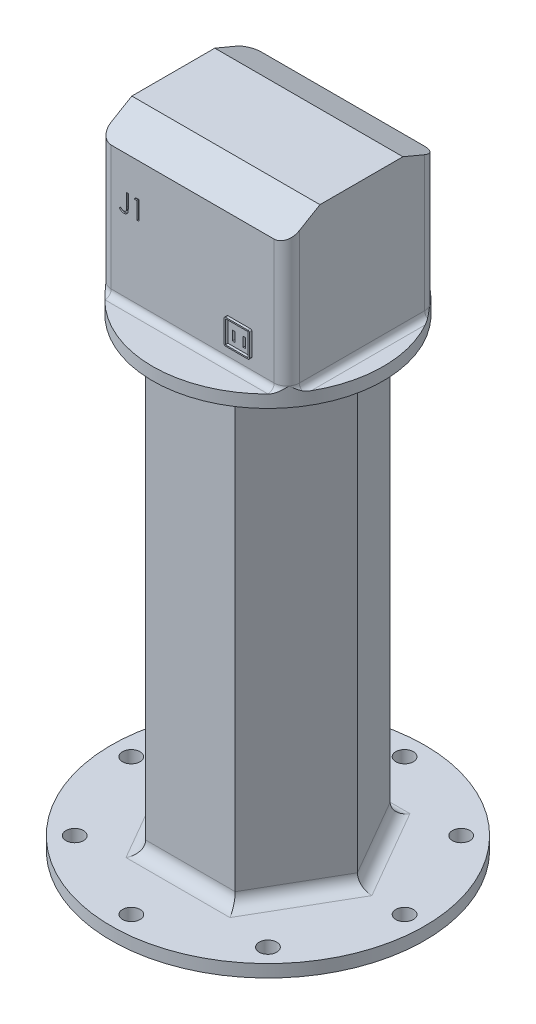
SolidWorks part; units mm, degrees
ref_plane "Alzado" through (0, 0, 0) normal (0, 0, 1) x (1, 0, 0)
ref_plane "Planta" through (0, 0, 0) normal (0, 1, 0) x (1, 0, 0)
ref_plane "Vista lateral" through (0, 0, 0) normal (1, 0, 0) x (0, 0, -1)
sketch "Sketch1" plane through (0, 0, 0) normal (0, 0, 1) x (1, 0, 0)
  line L1 (-75, -60) -> (75, -60)
  line L2 (-75, -60) -> (-75, 60)
  line L3 (-75, 60) -> (75, 60)
  line L4 (75, -60) -> (75, 60)
  line L5 (-75, -60) -> (75, 60) construction
  line L6 (-75, 60) -> (75, -60) construction
  point P0 (0, 0)
  dimension "D1" = 150
  dimension "D2" = 120
extrude "Boss-Extrude1" add sketch "Sketch1" along normal blind 60 and the other way blind 60
sketch "Sketch2" plane through (0, 0, 0) normal (0, 0, 1) x (1, 0, 0)
  line L5 (-75, 0) -> (-80, 0)
  line L6 (-75, 60) -> (-75, -60) construction
  line L7 (-80, 0) -> (-80, -36.1073)
  line L8 (-80, -36.1073) -> (-75, -44.4223)
  line L9 (-75, -44.4223) -> (-75, 0)
revolve "Revolve1" add sketch "Sketch2" angle 360 about L5
sketch "Sketch3" plane through (-80, 0, 0) normal (-1, 0, 0) x (0, 0, 1)
  circle A1 centre (0, 0) radius 12.5
  dimension "D1" = 25
extrude "Cut-Extrude2" cut sketch "Sketch3" against normal blind 10
sketch "Sketch4" plane through (0, -60, 0) normal (0, -1, 0) x (1, 0, 0)
  line L4 (69.9446, 45.0893) -> (69.9446, -45.0893)
  line L7 (-75, -60) -> (75, -60)
  line L12 (-75, -60) -> (-75, 60)
  line L13 (-75, 60) -> (75, 60)
  line L14 (75, -60) -> (75, 60)
  line L15 (1.8562, -5.2808) -> (58.2948, -49.733)
  line L16 (-58.2948, -49.733) -> (-1.8562, -5.2808)
  line L17 (-65.0883, -47.4461) -> (-7.8408, -2.3568)
  line L18 (-65.0883, 47.4461) -> (-7.8408, 2.3568)
  line L19 (-56.4386, -55.0898) -> (56.4386, -55.0898)
  line L20 (-69.9446, -45.0893) -> (-69.9446, 45.0893)
  line L21 (-56.4386, 55.0898) -> (56.4386, 55.0898)
  line L23 (-58.2948, 49.733) -> (-1.8562, 5.2808)
  line L26 (1.8562, 5.2808) -> (58.2948, 49.733)
  line L27 (7.8408, 2.3568) -> (65.0883, 47.4461)
  line L28 (7.8408, -2.3568) -> (65.0883, -47.4461)
  arc A4 (56.4386, -55.0898) -> (58.2948, -49.733) centre (56.4386, -52.0898) ccw
  arc A5 (69.9446, -45.0893) -> (65.0883, -47.4461) centre (66.9446, -45.0893) cw
  arc A6 (-56.4386, -55.0898) -> (-58.2948, -49.733) centre (-56.4386, -52.0898) cw
  arc A7 (-65.0883, -47.4461) -> (-69.9446, -45.0893) centre (-66.9446, -45.0893) cw
  arc A12 (7.8408, 2.3568) -> (7.8408, -2.3568) centre (9.697, 0) ccw
  arc A13 (1.8562, -5.2808) -> (-1.8562, -5.2808) centre (0, -7.6376) ccw
  arc A14 (-7.8408, -2.3568) -> (-7.8408, 2.3568) centre (-9.697, 0) ccw
  arc A15 (1.8562, 5.2808) -> (-1.8562, 5.2808) centre (0, 7.6376) cw
  arc A16 (69.9446, 45.0893) -> (65.0883, 47.4461) centre (66.9446, 45.0893) ccw
  arc A17 (58.2948, 49.733) -> (56.4386, 55.0898) centre (56.4386, 52.0898) ccw
  arc A18 (-69.9446, 45.0893) -> (-65.0883, 47.4461) centre (-66.9446, 45.0893) cw
  arc A19 (-58.2948, 49.733) -> (-56.4386, 55.0898) centre (-56.4386, 52.0898) cw
  point P0 (0, 0)
  point P7 (0, 0)
  point P30 (4.8485, 0)
  point P33 (0, -3.8188)
  dimension "D1" = 3
extrude "Boss-Extrude2" add sketch "Sketch4" along normal blind 2
sketch "Sketch6" plane through (0, 0, 60) normal (0, 0, 1) x (1, 0, 0)
  text T0 "J1" font "Century Gothic" height 15
extrude "Cut-Extrude4" cut sketch "Sketch6" against normal blind 1
sketch "Sketch7" plane through (-75, 0, 0) normal (-1, 0, 0) x (0, 0, 1)
  line L1 (-50, 60) -> (50, 60) construction
  line L9 (-82.4123, 72.1539) -> (68.864, 72.1539)
  line L10 (33.5423, 60) -> (68.864, 39.1539)
  line L11 (-82.4123, 72.1539) -> (-82.4123, 39.1539)
  line L12 (-82.4123, 39.1539) -> (-32.6153, 60)
  line L13 (68.864, 39.1539) -> (68.864, 72.1539)
  line L14 (-32.6153, 60) -> (33.5423, 60)
  dimension "D1" = 33
extrude "Cut-Extrude5" cut sketch "Sketch7" against normal blind 177
fillet "Fillet1" radius 10 4 edges at (75, -6.7319, -60) (75, -8.8074, 60) (-75, -6.7319, -60) (-75, -8.8074, 60)
sketch "Sketch8" plane through (0, 0, 60) normal (0, 0, 1) x (1, 0, 0)
  line L0 (46.811, -46.653) -> (47.1039, -46.9459) construction
  line L1 (28.1039, -26.9459) -> (46.1039, -26.9459)
  line L2 (27.1039, -27.9459) -> (27.1039, -45.9459)
  line L3 (28.1039, -46.9459) -> (46.1039, -46.9459)
  line L4 (47.1039, -27.9459) -> (47.1039, -45.9459)
  line L5 (27.1039, -26.9459) -> (27.3968, -27.2388) construction
  line L6 (27.1039, -46.9459) -> (27.3968, -46.653) construction
  line L7 (46.811, -27.2388) -> (47.1039, -26.9459) construction
  line L8 (28.1039, -27.9459) -> (46.1039, -27.9459)
  line L9 (46.1039, -27.9459) -> (46.1039, -45.9459)
  line L10 (28.1039, -45.9459) -> (46.1039, -45.9459)
  line L11 (28.1039, -27.9459) -> (28.1039, -45.9459)
  arc A0 (47.1039, -27.9459) -> (46.1039, -26.9459) centre (46.1039, -27.9459) ccw
  arc A1 (46.1039, -46.9459) -> (47.1039, -45.9459) centre (46.1039, -45.9459) ccw
  arc A2 (28.1039, -46.9459) -> (27.1039, -45.9459) centre (28.1039, -45.9459) cw
  arc A3 (27.1039, -27.9459) -> (28.1039, -26.9459) centre (28.1039, -27.9459) cw
  arc A4 (46.1039, -27.9459) -> (46.1039, -27.9459) centre (46.1039, -27.9459) ccw
  arc A5 (46.1039, -45.9459) -> (46.1039, -45.9459) centre (46.1039, -45.9459) ccw
  arc A6 (28.1039, -45.9459) -> (28.1039, -45.9459) centre (28.1039, -45.9459) cw
  arc A7 (28.1039, -27.9459) -> (28.1039, -27.9459) centre (28.1039, -27.9459) cw
  point P0 (37.1039, -36.9459)
  dimension "D3" = 1
  dimension "D1" = 20
  dimension "D2" = 20
  dimension "D4" = 1
extrude "Boss-Extrude3" add sketch "Sketch8" along normal blind 2
sketch "Sketch9" plane through (0, 0, 60) normal (0, 0, 1) x (1, 0, 0)
  line L1 (31.6246, -42.6103) -> (33.6246, -42.6103)
  line L2 (31.6246, -42.6103) -> (31.6246, -35.0386)
  line L3 (31.6246, -35.0386) -> (33.6246, -35.0386)
  line L4 (33.6246, -42.6103) -> (33.6246, -35.0386)
  line L5 (31.6246, -42.6103) -> (33.6246, -35.0386) construction
  line L6 (31.6246, -35.0386) -> (33.6246, -42.6103) construction
  line L7 (42.2434, -42.6103) -> (40.2434, -42.6103)
  line L8 (42.2434, -42.6103) -> (42.2434, -35.0386)
  line L9 (42.2434, -35.0386) -> (40.2434, -35.0386)
  line L10 (40.2434, -42.6103) -> (40.2434, -35.0386)
  line L11 (42.2434, -42.6103) -> (40.2434, -35.0386) construction
  line L12 (42.2434, -35.0386) -> (40.2434, -42.6103) construction
  point P0 (32.6246, -38.8245)
  point P5 (41.2434, -38.8245)
  dimension "D1" = 2
  dimension "D2" = 2
extrude "Cut-Extrude6" cut sketch "Sketch9" against normal blind 8
sketch "Sketch10" plane through (0, -60, 0) normal (0, -1, 0) x (1, 0, 0)
  circle A0 centre (0, 0) radius 92.0061
extrude "Boss-Extrude4" add sketch "Sketch10" along normal blind 10
sketch "Sketch11" plane through (0, -70, 0) normal (0, -1, 0) x (1, 0, 0)
  line L1 (71.3397, 0) -> (35.6698, 61.782)
  line L2 (35.6698, 61.782) -> (-35.6698, 61.782)
  line L3 (-35.6698, 61.782) -> (-71.3397, 0)
  line L4 (-71.3397, 0) -> (-35.6698, -61.782)
  line L5 (-35.6698, -61.782) -> (35.6698, -61.782)
  line L6 (35.6698, -61.782) -> (71.3397, 0)
  circle A0 centre (0, 0) radius 61.782 construction
extrude "Boss-Extrude5" add sketch "Sketch11" along normal blind 360
sketch "Sketch12" plane through (0, -430, 0) normal (0, -1, 0) x (1, 0, 0)
  circle A0 centre (0, 0) radius 125
  dimension "D1" = 250
extrude "Boss-Extrude6" add sketch "Sketch12" along normal blind 10
sketch "Sketch13" plane through (0, -430, 0) normal (0, 1, 0) x (1, 0, 0)
  circle A0 centre (0, 108.9534) radius 7
  circle A1 centre (77.0417, 77.0417) radius 7
  circle A2 centre (108.9534, 0) radius 7
  circle A3 centre (77.0417, -77.0417) radius 7
  circle A4 centre (0, -108.9534) radius 7
  circle A5 centre (-77.0417, -77.0417) radius 7
  circle A6 centre (-108.9534, 0) radius 7
  circle A7 centre (-77.0417, 77.0417) radius 7
  point P3 (0, 108.9534)
  point P18 (0, 0)
  dimension "D1" = 8
extrude "Cut-Extrude7" cut sketch "Sketch13" against normal blind 10
fillet "Fillet2" radius 10 6 edges at (-53.5048, -430, -30.891) (0, -430, -61.782) (53.5048, -430, -30.891) (53.5048, -430, 30.891) (0, -430, 61.782) (-53.5048, -430, 30.891)
fillet "Fillet3" radius 10 6 edges at (0, -70, 61.782) (-53.5048, -70, 30.891) (-53.5048, -70, -30.891) (0, -70, -61.782) (53.5048, -70, -30.891) (53.5048, -70, 30.891)
fillet "Fillet4" radius 5 8 edges at (69.4175, -60, 58.9714) (75, -60, 0) (69.4175, -60, -58.9714) (0, -60, -60) (-69.4175, -60, -58.9714) (-75, -60, 0) (-69.4175, -60, 58.9714) (0, -60, 60)
